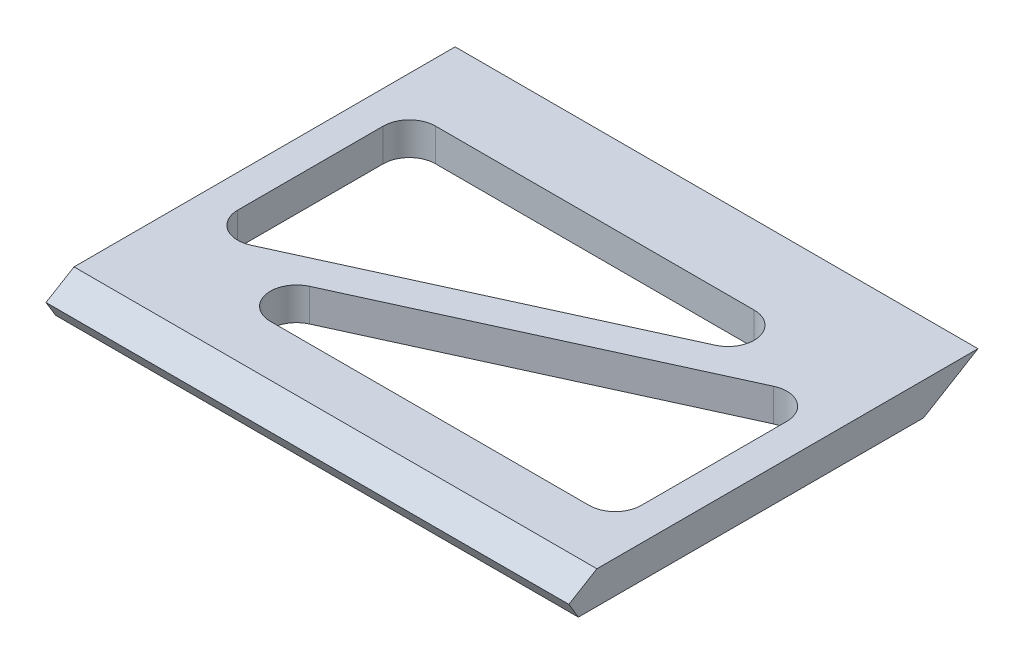
SolidWorks part; units mm, degrees
material "Balsa"
ref_plane "Front Plane" through (0, 0, 0) normal (0, 0, 1) x (1, 0, 0)
ref_plane "Top Plane" through (0, 0, 0) normal (0, 1, 0) x (1, 0, 0)
ref_plane "Right Plane" through (0, 0, 0) normal (1, 0, 0) x (0, 0, -1)
sketch "Sketch3" plane through (71.1933, 0, 0) normal (1, 0, 0) x (0, 0, -1)
  line L0 (56.968, 6.35) -> (46.3846, 0)
  line L1 (46.3846, 0) -> (-20.6804, 0)
  line L2 (-20.6804, 0) -> (-22.5302, 3.083)
  line L3 (-22.5302, 3.083) -> (-32.9848, 20.5072) construction
  line L5 (56.968, 6.35) -> (89.6384, 25.9523) construction
  line L6 (-22.5302, 3.083) -> (-17.0851, 6.35)
  line L7 (-17.0851, 6.35) -> (56.968, 6.35)
extrude "Boss-Extrude2" add sketch "Sketch3" against normal up to surface (101.6 mm away)
sketch "Sketch4" plane through (0, 6.35, 0) normal (0, 1, 0) x (1, 0, 0)
  line L0 (-30.4067, -17.0851) -> (-30.4067, 56.968) construction
  line L1 (-18.9767, 41.728) -> (42.949, 41.728)
  line L2 (-24.0567, 36.648) -> (-24.0567, 8.3732)
  line L3 (-2.1624, -7.1791) -> (59.7633, -7.1791)
  line L4 (64.8433, 26.1757) -> (64.8433, -2.0991)
  line L5 (-30.4067, 56.968) -> (71.1933, 56.968) construction
  line L6 (71.1933, 56.968) -> (71.1933, -17.0851) construction
  line L7 (-30.4067, -17.0851) -> (71.1933, -17.0851) construction
  line L8 (-16.8668, 3.7521) -> (45.0589, 32.0269)
  line L9 (-4.2724, 2.522) -> (57.6533, 30.7968)
  line L10 (-29.6117, -5.5575) -> (68.6464, 39.3064)
  arc A0 (-4.2724, 2.522) -> (-2.1624, -7.1791) centre (-2.1624, -2.0991) ccw
  arc A1 (59.7633, -7.1791) -> (64.8433, -2.0991) centre (59.7633, -2.0991) ccw
  arc A2 (57.6533, 30.7968) -> (64.8433, 26.1757) centre (59.7633, 26.1757) cw
  arc A3 (45.0589, 32.0269) -> (42.949, 41.728) centre (42.949, 36.648) ccw
  arc A4 (-18.9767, 41.728) -> (-24.0567, 36.648) centre (-18.9767, 36.648) ccw
  arc A5 (-16.8668, 3.7521) -> (-24.0567, 8.3732) centre (-18.9767, 8.3732) cw
  dimension "D7" = 5.08
  dimension "D1" = 6.35
  dimension "D2" = 15.24
  dimension "D3" = 6.35
  dimension "D4" = 9.906
  dimension "D5" = 3.175
  dimension "D6" = 3.175
extrude "Cut-Extrude1" cut sketch "Sketch4" against normal up to surface (6.35 mm away) contours A5 L8 A3 L1 A4 L2 | A2 L9 A0 L3 A1 L4 region at (4.1335, 6.35, -27.6167) region at (36.6531, 6.35, -6.9321) up to face at (20.3933, 0, -12.8521)
